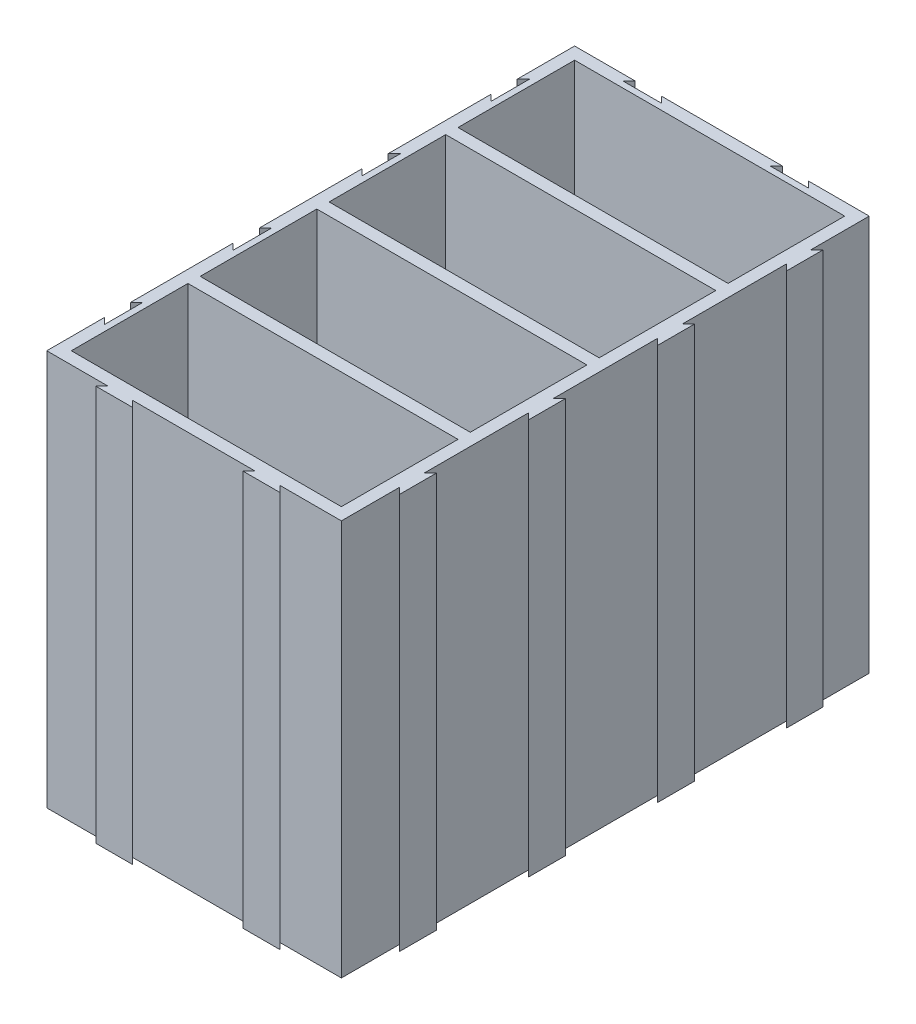
SolidWorks part; units mm, degrees
ref_plane "Спереди" through (0, 0, 0) normal (0, 0, 1) x (1, 0, 0)
ref_plane "Сверху" through (0, 0, 0) normal (0, 1, 0) x (1, 0, 0)
ref_plane "Справа" through (0, 0, 0) normal (1, 0, 0) x (0, 0, -1)
sketch "Эскиз1" plane through (0, 0, 0) normal (0, 1, 0) x (1, 0, 0)
  line L0 (0, 24.2143) -> (0, -22.6471) construction
  line L1 (0, -8.4) -> (0, 8.4) construction
  line L2 (-17.6, 0.8) -> (17.6, 0.8)
  line L3 (-17.6, 0.8) -> (-17.6, 16)
  line L4 (-17.6, 16) -> (17.6, 16)
  line L5 (17.6, 0.8) -> (17.6, 16)
  line L6 (-17.6, 0.8) -> (17.6, 16) construction
  line L7 (-17.6, 16) -> (17.6, 0.8) construction
  line L8 (-17.6, 17.6) -> (17.6, 17.6)
  line L9 (-17.6, 17.6) -> (-17.6, 32.8)
  line L10 (-17.6, 32.8) -> (17.6, 32.8)
  line L11 (17.6, 17.6) -> (17.6, 32.8)
  line L12 (-17.6, 17.6) -> (17.6, 32.8) construction
  line L13 (-17.6, 32.8) -> (17.6, 17.6) construction
  line L14 (-17.6, -16) -> (17.6, -16)
  line L15 (-17.6, -16) -> (-17.6, -0.8)
  line L16 (-17.6, -0.8) -> (17.6, -0.8)
  line L17 (17.6, -16) -> (17.6, -0.8)
  line L18 (-17.6, -16) -> (17.6, -0.8) construction
  line L19 (-17.6, -0.8) -> (17.6, -16) construction
  line L20 (-17.6, -32.8) -> (17.6, -32.8)
  line L21 (-17.6, -32.8) -> (-17.6, -17.6)
  line L22 (-17.6, -17.6) -> (17.6, -17.6)
  line L23 (17.6, -32.8) -> (17.6, -17.6)
  line L24 (-17.6, -32.8) -> (17.6, -17.6) construction
  line L25 (-17.6, -17.6) -> (17.6, -32.8) construction
  line L26 (-19.2, 26.9) -> (-18.4, 27.7)
  line L27 (-19.2, 34.4) -> (-11.3, 34.4)
  line L28 (-19.2, 34.4) -> (-19.2, 26.9)
  line L29 (-19.2, -34.4) -> (-11.2, -34.4)
  line L30 (19.2, 34.4) -> (19.2, 26.8)
  line L31 (-18.4, 27.7) -> (-18.4, 22.7)
  line L32 (-18.4, 22.7) -> (-19.2, 23.5)
  line L33 (19.2, 26.8) -> (20, 27.6)
  line L34 (20, 27.6) -> (20, 22.8)
  line L35 (20, 22.8) -> (19.2, 23.6)
  line L36 (20, 10.8) -> (20, 6)
  line L37 (19.2, 10) -> (20, 10.8)
  line L38 (20, 6) -> (19.2, 6.8)
  line L39 (20, -6) -> (20, -10.8)
  line L40 (19.2, -6.8) -> (20, -6)
  line L41 (20, -10.8) -> (19.2, -10)
  line L42 (20, -22.8) -> (20, -27.6)
  line L43 (19.2, -23.6) -> (20, -22.8)
  line L44 (20, -27.6) -> (19.2, -26.8)
  line L45 (-18.4, 10.9) -> (-18.4, 5.9)
  line L46 (-19.2, 10.1) -> (-18.4, 10.9)
  line L47 (-18.4, 5.9) -> (-19.2, 6.7)
  line L48 (-18.4, -5.9) -> (-18.4, -10.9)
  line L49 (-19.2, -6.7) -> (-18.4, -5.9)
  line L50 (-18.4, -10.9) -> (-19.2, -10.1)
  line L51 (-18.4, -22.7) -> (-18.4, -27.7)
  line L52 (-19.2, -23.5) -> (-18.4, -22.7)
  line L53 (-18.4, -27.7) -> (-19.2, -26.9)
  line L54 (-19.2, 23.5) -> (-19.2, 10.1)
  line L55 (-19.2, 6.7) -> (-19.2, -6.7)
  line L56 (-19.2, -10.1) -> (-19.2, -23.5)
  line L57 (-19.2, -26.9) -> (-19.2, -34.4)
  line L58 (19.2, 6.8) -> (19.2, -6.8)
  line L59 (19.2, -10) -> (19.2, -23.6)
  line L60 (19.2, -26.8) -> (19.2, -34.4)
  line L61 (19.2, 23.6) -> (19.2, 10)
  line L62 (11.2, -34.4) -> (12, -35.2)
  line L63 (12, -35.2) -> (7.2, -35.2)
  line L64 (7.2, -35.2) -> (8, -34.4)
  line L65 (-7.2, -35.2) -> (-12, -35.2)
  line L66 (-12, -35.2) -> (-11.2, -34.4)
  line L67 (-8, -34.4) -> (-7.2, -35.2)
  line L68 (7.9, 34.4) -> (7.1, 33.6)
  line L69 (7.1, 33.6) -> (12.1, 33.6)
  line L70 (12.1, 33.6) -> (11.3, 34.4)
  line L71 (-11.3, 34.4) -> (-12.1, 33.6)
  line L72 (-12.1, 33.6) -> (-7.1, 33.6)
  line L73 (-7.1, 33.6) -> (-7.9, 34.4)
  line L74 (-8, -34.4) -> (8, -34.4)
  line L75 (11.2, -34.4) -> (19.2, -34.4)
  line L76 (-7.9, 34.4) -> (7.9, 34.4)
  line L77 (11.3, 34.4) -> (19.2, 34.4)
  line L78 (-16.6, 27.7) -> (-3.5, 27.7)
  line L79 (-2.5, 31.8) -> (-2.5, 28.7)
  line L80 (2.5, 31.8) -> (2.5, 28.7)
  line L81 (16.6, 27.7) -> (3.5, 27.7)
  line L82 (-16.6, 22.7) -> (-3.5, 22.7)
  line L83 (-2.5, 18.6) -> (-2.5, 21.7)
  line L84 (2.5, 18.6) -> (2.5, 21.7)
  line L85 (16.6, 22.7) -> (3.5, 22.7)
  line L86 (-2.5, 1.8) -> (-2.5, 4.9)
  line L87 (-16.6, 5.9) -> (-3.5, 5.9)
  line L88 (-2.5, 15) -> (-2.5, 11.9)
  line L89 (-16.6, 10.9) -> (-3.5, 10.9)
  line L90 (2.5, 15) -> (2.5, 11.9)
  line L91 (16.6, 10.9) -> (3.5, 10.9)
  line L92 (16.6, 5.9) -> (3.5, 5.9)
  line L93 (2.5, 1.8) -> (2.5, 4.9)
  line L94 (-2.5, -15) -> (-2.5, -11.9)
  line L95 (-16.6, -10.9) -> (-3.5, -10.9)
  line L96 (-2.5, -1.8) -> (-2.5, -4.9)
  line L97 (-16.6, -5.9) -> (-3.5, -5.9)
  line L98 (2.5, -1.8) -> (2.5, -4.9)
  line L99 (16.6, -5.9) -> (3.5, -5.9)
  line L100 (16.6, -10.9) -> (3.5, -10.9)
  line L101 (2.5, -15) -> (2.5, -11.9)
  line L102 (-2.5, -31.8) -> (-2.5, -28.7)
  line L103 (-16.6, -27.7) -> (-3.5, -27.7)
  line L104 (-2.5, -18.6) -> (-2.5, -21.7)
  line L105 (-16.6, -22.7) -> (-3.5, -22.7)
  line L106 (2.5, -18.6) -> (2.5, -21.7)
  line L107 (16.6, -22.7) -> (3.5, -22.7)
  line L108 (16.6, -27.7) -> (3.5, -27.7)
  line L109 (2.5, -31.8) -> (2.5, -28.7)
  arc A0 (-16.6, 32.8) -> (-17.6, 31.8) centre (-16.6, 31.8) ccw
  arc A1 (-2.5, 31.8) -> (-3.5, 32.8) centre (-3.5, 31.8) ccw
  arc A2 (3.5, 32.8) -> (2.5, 31.8) centre (3.5, 31.8) ccw
  arc A3 (2.5, 18.6) -> (3.5, 17.6) centre (3.5, 18.6) ccw
  arc A4 (-3.5, 17.6) -> (-2.5, 18.6) centre (-3.5, 18.6) ccw
  arc A5 (-17.6, 18.6) -> (-16.6, 17.6) centre (-16.6, 18.6) ccw
  arc A6 (17.6, 31.8) -> (16.6, 32.8) centre (16.6, 31.8) ccw
  arc A7 (16.6, 17.6) -> (17.6, 18.6) centre (16.6, 18.6) ccw
  arc A8 (-17.6, 28.7) -> (-16.6, 27.7) centre (-16.6, 28.7) ccw
  arc A9 (-16.6, 22.7) -> (-17.6, 21.7) centre (-16.6, 21.7) ccw
  arc A10 (-3.5, 27.7) -> (-2.5, 28.7) centre (-3.5, 28.7) ccw
  arc A11 (-2.5, 21.7) -> (-3.5, 22.7) centre (-3.5, 21.7) ccw
  arc A12 (2.5, 28.7) -> (3.5, 27.7) centre (3.5, 28.7) ccw
  arc A13 (3.5, 22.7) -> (2.5, 21.7) centre (3.5, 21.7) ccw
  arc A14 (16.6, 27.7) -> (17.6, 28.7) centre (16.6, 28.7) ccw
  arc A15 (17.6, 21.7) -> (16.6, 22.7) centre (16.6, 21.7) ccw
  arc A16 (-3.5, 0.8) -> (-2.5, 1.8) centre (-3.5, 1.8) ccw
  arc A17 (-2.5, 4.9) -> (-3.5, 5.9) centre (-3.5, 4.9) ccw
  arc A18 (-17.6, 1.8) -> (-16.6, 0.8) centre (-16.6, 1.8) ccw
  arc A19 (-16.6, 5.9) -> (-17.6, 4.9) centre (-16.6, 4.9) ccw
  arc A20 (-17.6, 11.9) -> (-16.6, 10.9) centre (-16.6, 11.9) ccw
  arc A21 (-16.6, 16) -> (-17.6, 15) centre (-16.6, 15) ccw
  arc A22 (-2.5, 15) -> (-3.5, 16) centre (-3.5, 15) ccw
  arc A23 (-3.5, 10.9) -> (-2.5, 11.9) centre (-3.5, 11.9) ccw
  arc A24 (2.5, 11.9) -> (3.5, 10.9) centre (3.5, 11.9) ccw
  arc A25 (3.5, 16) -> (2.5, 15) centre (3.5, 15) ccw
  arc A26 (16.6, 10.9) -> (17.6, 11.9) centre (16.6, 11.9) ccw
  arc A27 (17.6, 15) -> (16.6, 16) centre (16.6, 15) ccw
  arc A28 (16.6, 0.8) -> (17.6, 1.8) centre (16.6, 1.8) ccw
  arc A29 (17.6, 4.9) -> (16.6, 5.9) centre (16.6, 4.9) ccw
  arc A30 (3.5, 5.9) -> (2.5, 4.9) centre (3.5, 4.9) ccw
  arc A31 (2.5, 1.8) -> (3.5, 0.8) centre (3.5, 1.8) ccw
  arc A32 (-3.5, -16) -> (-2.5, -15) centre (-3.5, -15) ccw
  arc A33 (-2.5, -11.9) -> (-3.5, -10.9) centre (-3.5, -11.9) ccw
  arc A34 (-17.6, -15) -> (-16.6, -16) centre (-16.6, -15) ccw
  arc A35 (-16.6, -10.9) -> (-17.6, -11.9) centre (-16.6, -11.9) ccw
  arc A36 (-17.6, -4.9) -> (-16.6, -5.9) centre (-16.6, -4.9) ccw
  arc A37 (-16.6, -0.8) -> (-17.6, -1.8) centre (-16.6, -1.8) ccw
  arc A38 (-2.5, -1.8) -> (-3.5, -0.8) centre (-3.5, -1.8) ccw
  arc A39 (-3.5, -5.9) -> (-2.5, -4.9) centre (-3.5, -4.9) ccw
  arc A40 (2.5, -4.9) -> (3.5, -5.9) centre (3.5, -4.9) ccw
  arc A41 (3.5, -0.8) -> (2.5, -1.8) centre (3.5, -1.8) ccw
  arc A42 (16.6, -5.9) -> (17.6, -4.9) centre (16.6, -4.9) ccw
  arc A43 (17.6, -1.8) -> (16.6, -0.8) centre (16.6, -1.8) ccw
  arc A44 (16.6, -16) -> (17.6, -15) centre (16.6, -15) ccw
  arc A45 (17.6, -11.9) -> (16.6, -10.9) centre (16.6, -11.9) ccw
  arc A46 (3.5, -10.9) -> (2.5, -11.9) centre (3.5, -11.9) ccw
  arc A47 (2.5, -15) -> (3.5, -16) centre (3.5, -15) ccw
  arc A48 (-3.5, -32.8) -> (-2.5, -31.8) centre (-3.5, -31.8) ccw
  arc A49 (-2.5, -28.7) -> (-3.5, -27.7) centre (-3.5, -28.7) ccw
  arc A50 (-17.6, -31.8) -> (-16.6, -32.8) centre (-16.6, -31.8) ccw
  arc A51 (-16.6, -27.7) -> (-17.6, -28.7) centre (-16.6, -28.7) ccw
  arc A52 (-17.6, -21.7) -> (-16.6, -22.7) centre (-16.6, -21.7) ccw
  arc A53 (-16.6, -17.6) -> (-17.6, -18.6) centre (-16.6, -18.6) ccw
  arc A54 (-2.5, -18.6) -> (-3.5, -17.6) centre (-3.5, -18.6) ccw
  arc A55 (-3.5, -22.7) -> (-2.5, -21.7) centre (-3.5, -21.7) ccw
  arc A56 (2.5, -21.7) -> (3.5, -22.7) centre (3.5, -21.7) ccw
  arc A57 (3.5, -17.6) -> (2.5, -18.6) centre (3.5, -18.6) ccw
  arc A58 (16.6, -22.7) -> (17.6, -21.7) centre (16.6, -21.7) ccw
  arc A59 (17.6, -18.6) -> (16.6, -17.6) centre (16.6, -18.6) ccw
  arc A60 (16.6, -32.8) -> (17.6, -31.8) centre (16.6, -31.8) ccw
  arc A61 (17.6, -28.7) -> (16.6, -27.7) centre (16.6, -28.7) ccw
  arc A62 (3.5, -27.7) -> (2.5, -28.7) centre (3.5, -28.7) ccw
  arc A63 (2.5, -31.8) -> (3.5, -32.8) centre (3.5, -31.8) ccw
  point P1 (0, 8.4)
  point P8 (0, 25.2)
  point P13 (0, -8.4)
  point P18 (0, -25.2)
  point P26 (0, 0)
  point P32 (-18.4, 25.2)
  point P38 (20, 25.2)
  point P66 (9.6, -35.2)
  point P68 (-9.6, -35.2)
  point P76 (9.6, 33.6)
  dimension "D25" = 1
  dimension "D1" = 35.2
  dimension "D2" = 15.2
  dimension "D3" = 1.6
  dimension "D4" = 1.6
  dimension "D5" = 1.6
  dimension "D6" = 1.6
  dimension "D7" = 1.6
  dimension "D8" = 1.6
  dimension "D9" = 1.6
  dimension "D10" = 5
  dimension "D11" = 45
  dimension "D12" = 0.8
  dimension "D15" = 0.8
  dimension "D16" = 4.8
  dimension "D17" = 45
  dimension "D18" = 9.6
  dimension "D21" = 5
  dimension "D22" = 2.5
  dimension "D23" = 5
  dimension "D24" = 2.5
  dimension "D27" = 45
  dimension "D28" = 0.8
  dimension "D29" = 4.8
  dimension "D31" = 45
  dimension "D32" = 0.8
  dimension "D33" = 5
  dimension "D13" = 1
  dimension "D14" = 4
  dimension "D19" = 2
  dimension "D20" = 1
  dimension "D26" = 4
  dimension "D30" = 4
  dimension "D34" = 2
extrude "Бобышка-Вытянуть1" add sketch "Эскиз1" along normal blind 1.6 contours L27 L28 L26 L31 L32 L54 L46 L45 L47 L55 L49 L48 L50 L56 L52 L51 L53 L57 L29 L66 L65 L67 L74 L64 L63 L62 L75 L38 L37 L61 L30 L72 | A63 L109 A62 L108 A61 L23 A58 L107 A56 L106 A57 L22 A54 L104 A55 L105 A52 L21 A51 L103 A49 L102 A48 L20 | A47 L101 A46 L100 A45 L17 A42 L99 A40 L98 A41 L16 A38 L96 A39 L97 A36 L15 A35 L95 A33 L94 A32 L14 | A31 L93 A30 L92 A29 L5 A26 L91 A24 L90 A25 L4 A22 L88 A23 L89 A20 L3 A19 L87 A17 L86 A16 L2 | A15 L11 A14 L81 A12 L80 A2 L10 A1 L79 A10 L78 A8 L9 A9 L82 A11 L83 A4 L8 A3 L84 A13 L85 | A0 L10 L9 | A6 L11 L10 | A7 L8 L11 | A27 L5 L4 | A28 L2 L5 | A43 L17 L16 | A44 L14 L17 | A59 L23 L22 | A60 L20 L23 | A50 L21 L20 | A34 L15 L14 | A53 L22 L21 | A18 L3 L2 | A37 L16 L15 | A5 L9 L8 | A21 L4 L3 region at (-17.3766, 0, -1.0234) region at (0, 0, -8.4) region at (17.3766, 0, -1.0234) region at (-17.3766, 0, -15.7766) region at (17.3766, 0, -15.7766) region at (-17.3766, 0, -17.8234) region at (0, 0, -25.2) region at (17.3766, 0, -17.8234) region at (-17.3766, 0, -32.5766) region at (17.3766, 0, -32.5766) region at (-17.3766, 0, 15.7766) region at (0, 0, 8.4) region at (17.3766, 0, 15.7766) region at (-17.3766, 0, 1.0234) region at (17.3766, 0, 1.0234) region at (-17.3766, 0, 32.5766) region at (0, 0, 25.2) region at (17.3766, 0, 32.5766) region at (-17.3766, 0, 17.8234) region at (17.3766, 0, 17.8234) region at (-18.4012, 0, -30.65)
extrude "Бобышка-Вытянуть2" add sketch "Эскиз1<3>" along normal blind 50 from offset 1.6 contours L27 L28 L26 L31 L32 L54 L46 L45 L47 L55 L49 L48 L50 L56 L52 L51 L53 L57 L29 L66 L65 L67 L74 L64 L63 L62 L75 L38 L37 L61 L30 L72 region at (-18.4012, 0, -30.65)
sketch "Эскиз1<3>" plane through (0, 0, 0) normal (0, 1, 0) x (1, 0, 0) same geometry as "Эскиз1"
equation "\"D18@Эскиз1\"=(35.2+1.6*2)/4"
